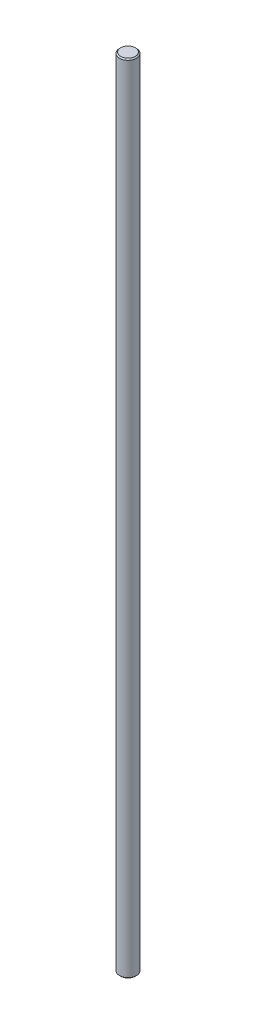
SolidWorks part; units mm, degrees
ref_plane "Front Plane" through (0, 0, 0) normal (0, 0, 1) x (1, 0, 0)
ref_plane "Top Plane" through (0, 0, 0) normal (0, 1, 0) x (1, 0, 0)
ref_plane "Right Plane" through (0, 0, 0) normal (1, 0, 0) x (0, 0, -1)
sketch "Sketch1" plane through (0, 0, 0) normal (0, 1, 0) x (1, 0, 0)
  circle A0 centre (0, 0) radius 7.5
  dimension "D1" = 15
extrude "Boss-Extrude1" add sketch "Sketch1" along normal blind 700
chamfer "Chamfer1" distance 1 angle 45 2 edges at (0, 700, 7.5) (0, 0, 7.5)
